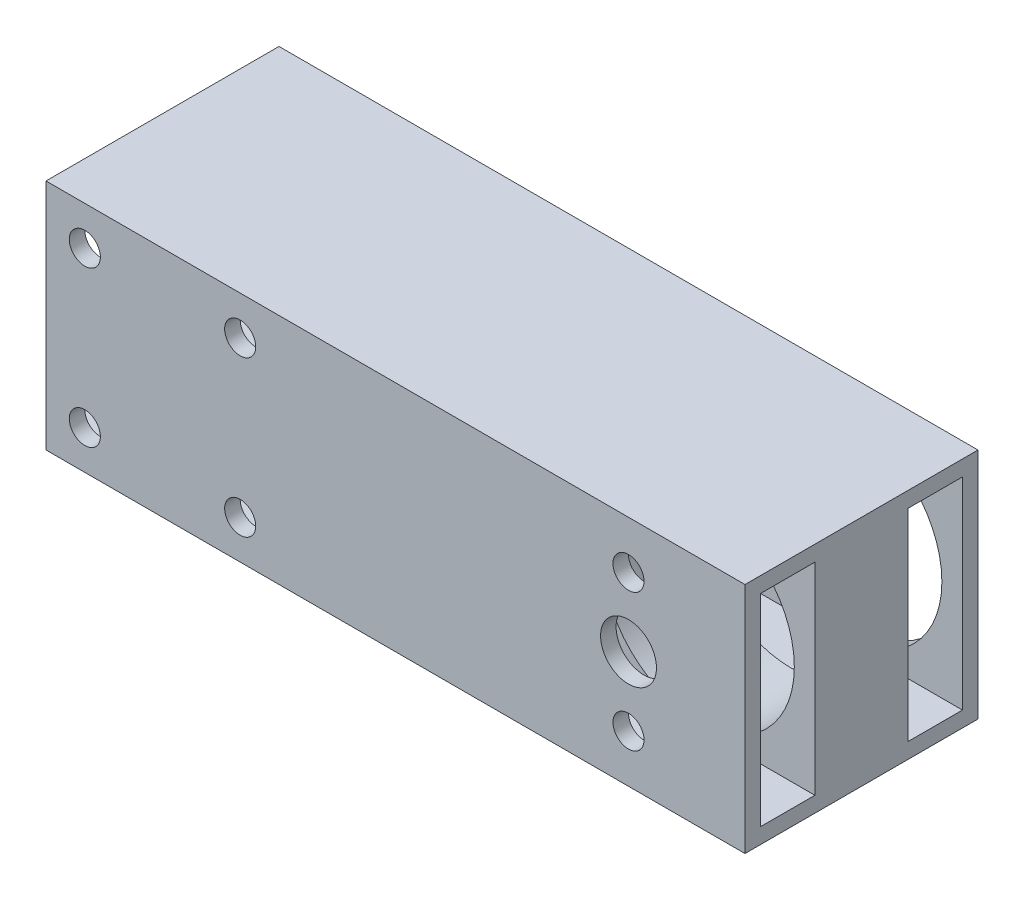
SolidWorks part; units mm, degrees
ref_plane "Front Plane" through (0, 0, 0) normal (0, 0, 1) x (1, 0, 0)
ref_plane "Top Plane" through (0, 0, 0) normal (0, 1, 0) x (1, 0, 0)
ref_plane "Right Plane" through (0, 0, 0) normal (1, 0, 0) x (0, 0, -1)
sketch "Sketch1" plane through (0, 0, 0) normal (1, 0, 0) x (0, 0, -1)
  line L1 (-15, -15) -> (15, -15)
  line L2 (-15, -15) -> (-15, 15)
  line L3 (-15, 15) -> (15, 15)
  line L4 (15, -15) -> (15, 15)
  line L5 (-15, -15) -> (15, 15) construction
  line L6 (-15, 15) -> (15, -15) construction
  line L11 (-5.1844, 5.1844) -> (5.1844, -5.1844) construction
  line L12 (-5.1844, -5.1844) -> (5.1844, 5.1844) construction
  line L13 (-13, 13) -> (-6, 13)
  line L14 (-13, 13) -> (-13, -13)
  line L15 (-13, -13) -> (-6, -13)
  line L16 (-6, 13) -> (-6, -13)
  line L17 (13, 13) -> (6, 13)
  line L18 (13, 13) -> (13, -13)
  line L19 (13, -13) -> (6, -13)
  line L20 (6, 13) -> (6, -13)
  point P0 (0, 0)
  point P7 (0, 0)
  dimension "D1" = 30
  dimension "D2" = 30
  dimension "D3" = 2
  dimension "D4" = 7
  dimension "D5" = 2
  dimension "D6" = 7
  dimension "D7" = 2
  dimension "D8" = 2
extrude "Boss-Extrude3" add sketch "Sketch1" along normal blind 90
sketch "Sketch6" plane through (0, 0, -15) normal (0, 0, -1) x (-1, 0, 0)
  line L0 (-90, -15) -> (-90, 15) construction
  circle A0 centre (-75, 0) radius 12.35
  dimension "D2" = 24.7
  dimension "D1" = 15
extrude "Cut-Extrude5" cut sketch "Sketch6" against normal blind 23
sketch "Sketch8" plane through (0, 0, 15) normal (0, 0, 1) x (1, 0, 0)
  line L0 (90, 15) -> (90, -15) construction
  circle A0 centre (75, 0) radius 3.6
  circle A1 centre (75, 8.85) radius 2
  circle A2 centre (75, -8.85) radius 2
  dimension "D2" = 7.2
  dimension "D5" = 4
  dimension "D6" = 4
  dimension "D1" = 15
  dimension "D3" = 8.85
  dimension "D4" = 8.85
extrude "Cut-Extrude6" cut sketch "Sketch8" against normal blind 17
sketch "Sketch9" plane through (0, 0, 0) normal (-1, 0, 0) x (0, 0, 1)
  line L0 (-6, 13) -> (6, 13)
  line L1 (-6, -13) -> (6, -13)
  line L2 (-6, 13) -> (-6, -13)
  line L3 (6, 13) -> (6, -13)
extrude "Cut-Extrude7" cut sketch "Sketch9" against normal blind 59
sketch "Sketch10" plane through (0, 0, -15) normal (0, 0, -1) x (-1, 0, 0)
  line L0 (0, 15) -> (-30.0029, 15)
  line L1 (-90, 15) -> (0, 15) construction
  line L2 (-30.0029, 15) -> (-30.0029, -15)
  line L3 (-90, -15) -> (0, -15) construction
  line L4 (-30.0029, -15) -> (0, -15)
  line L5 (-25.0029, 10) -> (0, 10)
  line L6 (0, -15) -> (0, 15) construction
  line L7 (-25.0029, 10) -> (-25.0029, -15)
  circle A0 centre (-25.0029, 10) radius 2
  circle A1 centre (-5, 10) radius 2
  circle A2 centre (-25.0029, -10) radius 2
  circle A3 centre (-5, -10) radius 2
  dimension "D3" = 4
  dimension "D4" = 5
  dimension "D5" = 4
  dimension "D7" = 4
  dimension "D8" = 4
  dimension "D1" = 5
  dimension "D2" = 5
  dimension "D6" = 5
extrude "Cut-Extrude8" cut sketch "Sketch10" against normal blind 34 contours A0 | A1 | A3 | A2
